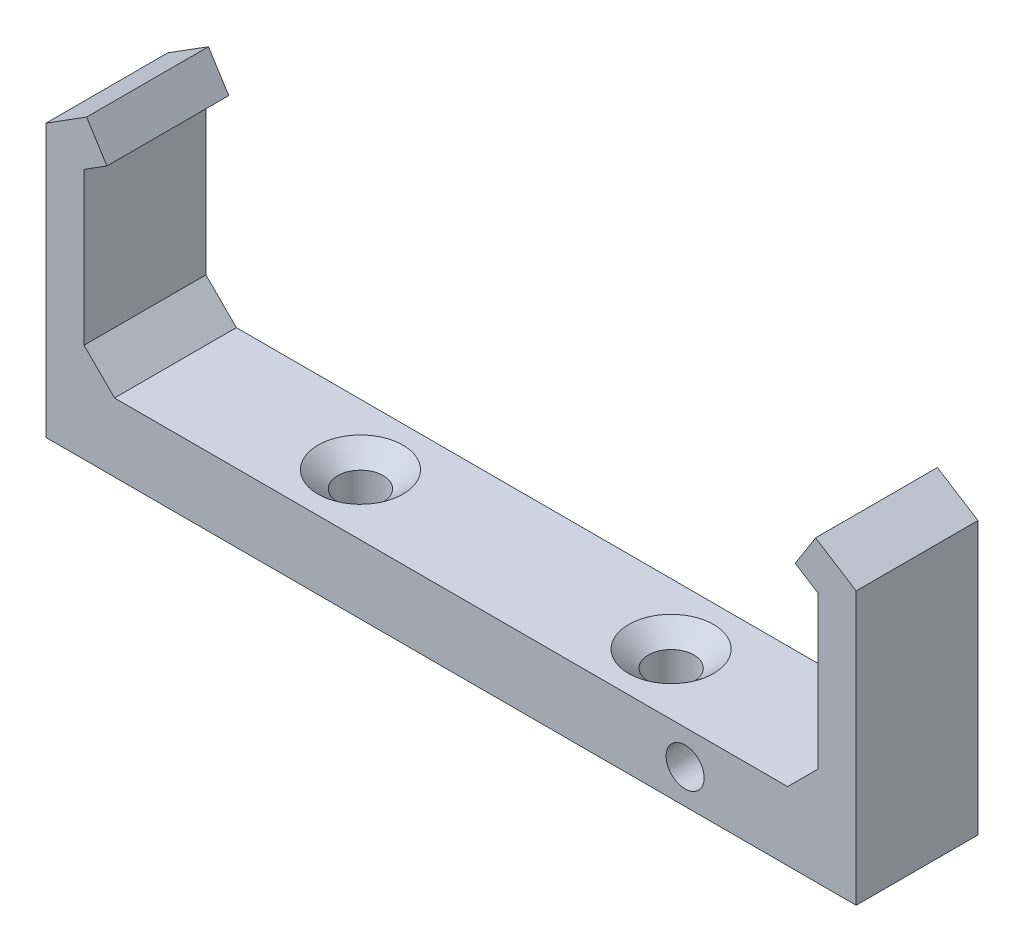
SolidWorks part; units mm, degrees
ref_plane "Front Plane" through (0, 0, 0) normal (0, 0, 1) x (1, 0, 0)
ref_plane "Top Plane" through (0, 0, 0) normal (0, 1, 0) x (1, 0, 0)
ref_plane "Right Plane" through (0, 0, 0) normal (1, 0, 0) x (0, 0, -1)
sketch "Sketch1" plane through (0, 0, 0) normal (0, 0, 1) x (1, 0, 0)
  line L0 (-0.3175, 0.0705) -> (30.2895, 0.0705)
  line L1 (30.2895, 0.0705) -> (-30.9245, 0.0705)
  line L2 (-30.7113, 19.1967) -> (-34.0995, 17.0632)
  line L3 (-30.9245, 0.0705) -> (-30.9245, 15.3105)
  line L4 (28.3845, 16.51) -> (30.2895, 15.3105)
  line L5 (-0.3175, 0.0705) -> (-0.3175, 33.7669) construction
  line L6 (-29.0195, 16.51) -> (-30.9245, 15.3105)
  line L7 (30.2895, 15.3105) -> (30.2895, 0.0705)
  line L8 (-34.0995, -3.1045) -> (-34.0995, 17.0632)
  line L9 (33.4645, -3.1045) -> (-34.0995, -3.1045)
  line L10 (30.0763, 19.1967) -> (33.4645, 17.0632)
  line L11 (30.2895, -3.1045) -> (-34.0995, -3.1045) construction
  line L12 (33.4645, -3.1045) -> (33.4645, 17.0632)
  line L13 (28.3845, 16.51) -> (30.0763, 19.1967)
  line L14 (-29.0195, 16.51) -> (-30.7113, 19.1967)
  line L15 (33.4645, 17.0632) -> (33.4645, 0.0705) construction
  line L16 (-30.9245, 0.0705) -> (-34.0995, 0.0705) construction
  line L17 (-29.0195, 16.51) -> (28.3845, 16.51) construction
  point P8 (0, 15.494)
  dimension "D1" = 61.214
  dimension "D2" = 3.175
  dimension "D4" = 3.175
  dimension "D5" = 2.2512
  dimension "D6" = 15.24
extrude "Boss-Extrude1" add sketch "Sketch1" along normal blind 5.08 and the other way blind 5.08 contours L6 L14 L2 L8 L9 L12 L10 L13 L4 L7 L0 L1 L3 region at (14.986, -0.641, 0)
sketch "Sketch2" plane through (0, 0, 0) normal (0, 1, 0) x (1, 0, 0)
  line L0 (0, 10.489) -> (0, -8.2714) construction
  line L2 (33.4645, -5.08) -> (-34.0995, -5.08) construction
  line L3 (33.4645, 5.08) -> (-34.0995, 5.08) construction
  line L6 (-34.0995, 0) -> (40.185, 0) construction
  line L7 (-34.0995, 5.08) -> (-34.0995, -5.08) construction
  circle A0 centre (-12.954, 0) radius 1.5875
  circle A1 centre (12.954, 0) radius 1.5875
  point P3 (-0.3175, -5.08)
  point P5 (-0.3175, 5.08)
  point P19 (-12.954, 0)
  dimension "D1" = 33.782
  dimension "D2" = 12.954
extrude "Cut-Extrude1" cut sketch "Sketch2" against normal blind 11.557 and the other way blind 3.175
chamfer "Chamfer1" distance 2.54 angle 45 1 edges at (30.2895, 0.0705, 0)
chamfer "Chamfer2" distance 2.54 angle 45 1 edges at (-30.9245, 0.0705, 0)
hole_wizard "CSK for #6 Flat Head Machine Screw (100)2" positions "3DSketch2" profile "Sketch5" countersink size "#6" standard "ANSI Inch" end condition through all
sketch3d "3DSketch2"
  line L0 (-12.954, 0.0705, 0) -> (-12.954, -3.1045, 0) construction
  line L1 (12.954, 0.0705, 0) -> (12.954, -3.1045, 0) construction
  point P0 (-12.954, 0.0705, 0)
  point P4 (12.954, 0.0705, 0)
sketch "Sketch5" plane through (-12.954, 0.0705, 0) normal (1, 0, 0) x (0, 0, 1)
  line L0 (0, 0) -> (0, 3.175)
  line L1 (0, 3.175) -> (1.8986, 3.175)
  line L2 (1.8986, 3.175) -> (1.8986, 1.38)
  line L3 (1.8986, 1.38) -> (3.5433, 0)
  line L5 (3.5433, 0) -> (0, 0)
  line L6 (-1.8986, 1.38) -> (-3.5433, 0) construction
  line L11 (0, -6.35) -> (0, 107.95) construction
  dimension "Thru Hole Dia." = 3.7973
  dimension "Thru Hole Depth" = 3.175
  dimension "Near C'Sink Dia." = 7.0866
  dimension "Near C'Sink Angle" = 100
ref_plane "Plane1" through (0, -3.1045, 0) normal (0, -1, 0) x (-1, 0, 0)
sketch "Sketch6" plane through (0, -3.1045, 0) normal (0, -1, 0) x (-1, 0, 0)
  line L1 (34.0995, -5.08) -> (-33.4645, -5.08)
  line L2 (34.0995, -5.08) -> (34.0995, 5.08)
  line L3 (34.0995, 5.08) -> (-33.4645, 5.08)
  line L4 (-33.4645, -5.08) -> (-33.4645, 5.08)
  circle A0 centre (12.954, 0) radius 1.8986
  circle A1 centre (-12.954, 0) radius 1.8986
extrude "Boss-Extrude2" add sketch "Sketch6" along normal blind 2.54
sketch "Sketch7" plane through (0, 0, 0) normal (0, 0, 1) x (1, 0, 0)
  line L1 (19.2005, -2.787) -> (19.2005, 0.0705) construction
  line L2 (-28.3845, 0.0705) -> (27.7495, 0.0705) construction
  line L3 (19.2005, 0.0705) -> (19.2005, -5.6445) construction
  line L4 (33.4645, -5.6445) -> (-34.0995, -5.6445) construction
  circle A0 centre (19.2005, -2.787) radius 1.5875
extrude "Cut-Extrude2" cut sketch "Sketch7" against normal through all and the other way through all
